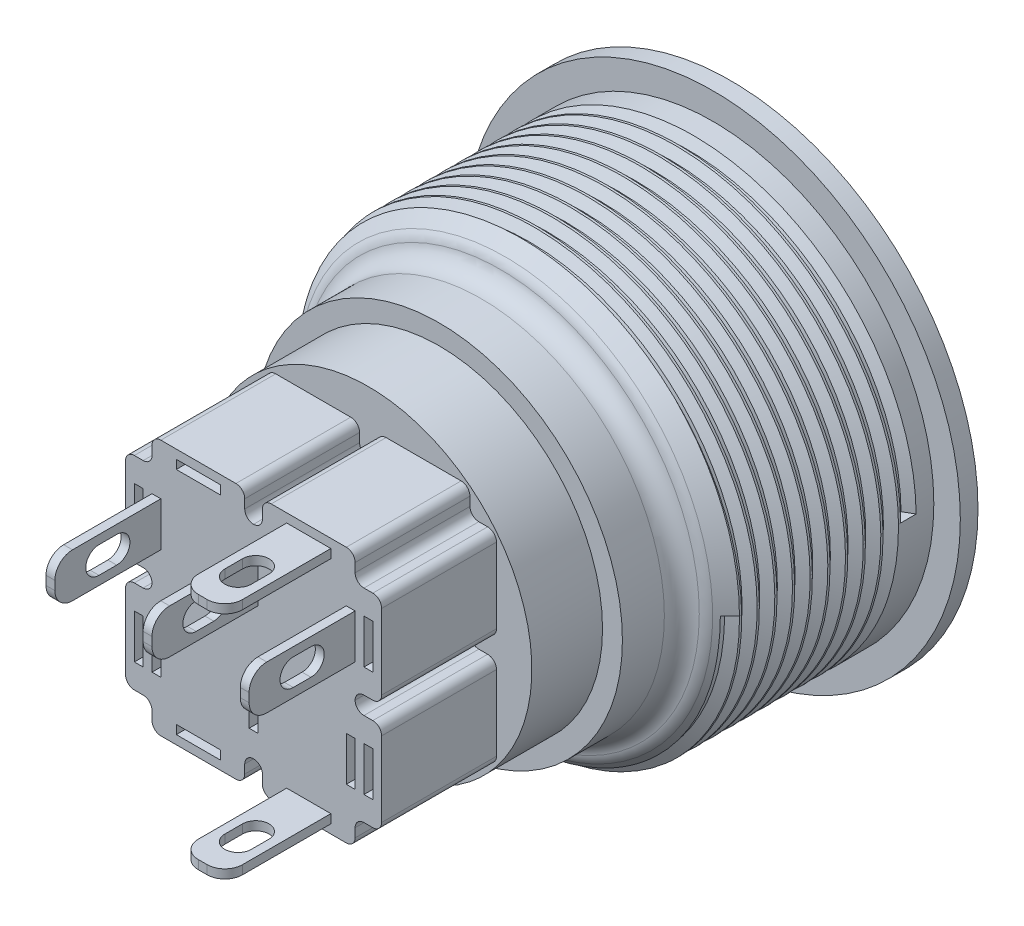
SolidWorks part; units mm, degrees
material "6061-O (SS)"
ref_plane "Ön Düzlem" through (0, 0, 0) normal (0, 0, 1) x (1, 0, 0)
ref_plane "Üst Düzlem" through (0, 0, 0) normal (0, 1, 0) x (1, 0, 0)
ref_plane "Sağ Düzlem" through (0, 0, 0) normal (1, 0, 0) x (0, 0, -1)
sketch "Çizim3" plane through (0, 0, 0) normal (0, 1, 0) x (1, 0, 0)
  line L0 (0, 0) -> (-14, 0) construction
  line L1 (-14, 0) -> (-14, 1) construction
  line L2 (-14, 1) -> (-12, 2) construction
  line L3 (-12, 2) -> (0, 2) construction
  line L4 (0, 2) -> (0, 0) construction
  line L5 (-11, 2) -> (-11, 0)
  line L6 (-11, 0) -> (-14, 0)
  line L7 (-14, 0) -> (-14, 1)
  line L8 (-14, 1) -> (-12, 2)
  line L9 (-12, 2) -> (-11, 2)
  dimension "D1" = 1
  dimension "D2" = 2
  dimension "D3" = 14
  dimension "D4" = 11
  dimension "D5" = 1
revolve "Döndür1" add sketch "Çizim3" angle 360 about L4
sketch "Çizim5" plane through (0, 0, 0) normal (0, 0, 1) x (1, 0, 0)
  circle A0 centre (0, 0) radius 11 construction
  circle A1 centre (0, 0) radius 11
extrude "Yükseklik-Ekstrüzyon2" add sketch "Çizim5" against normal blind 1.9
sketch "Çizim6" plane through (0, 0, -1.9) normal (0, 0, -1) x (-1, 0, 0)
  line L0 (0, 0) -> (-3.8891, 3.8891) construction
  line L1 (0, 0) -> (0, 5.5) construction
  line L2 (0, 0) -> (3.8891, 3.8891) construction
  line L3 (-3.5178, 3.5178) -> (-3.1623, 3.1623)
  line L4 (3.5178, 3.5178) -> (3.1623, 3.1623)
  line L5 (0, 6) -> (0, 1) construction
  line L6 (-0.75, 5.1059) -> (-0.75, 1.1059)
  line L7 (0.75, 5.1059) -> (0.75, 1.1059)
  line L8 (-0.25, 0.6059) -> (0.25, 0.6059)
  line L9 (-0.25, 5.6059) -> (0.25, 5.6059)
  line L10 (-0.75, 6) -> (-0.75, 1) construction
  line L11 (0.75, 6) -> (0.75, 1) construction
  arc A0 (-3.1252, 2.4966) -> (3.1252, 2.4966) centre (0, 0) ccw
  arc A1 (-4.2585, 3.4807) -> (4.2585, 3.4807) centre (0, 0) ccw
  circle A2 centre (0, 0) radius 5.5 construction
  circle A3 centre (0, 0) radius 4 construction
  arc A4 (3.5178, 3.5178) -> (4.2585, 3.4807) centre (3.8714, 3.1643) cw
  arc A5 (3.1623, 3.1623) -> (3.1252, 2.4966) centre (3.5158, 2.8087) ccw
  arc A6 (-3.1623, 3.1623) -> (-3.1252, 2.4966) centre (-3.5158, 2.8087) cw
  arc A7 (-3.5178, 3.5178) -> (-4.2585, 3.4807) centre (-3.8714, 3.1643) ccw
  arc A8 (-0.25, 0.6059) -> (-0.75, 1.1059) centre (-0.25, 1.1059) cw
  arc A9 (0.25, 0.6059) -> (0.75, 1.1059) centre (0.25, 1.1059) ccw
  arc A10 (0.75, 5.1059) -> (0.25, 5.6059) centre (0.25, 5.1059) ccw
  arc A11 (-0.25, 5.6059) -> (-0.75, 5.1059) centre (-0.25, 5.1059) ccw
  point P15 (2.8284, 2.8284)
  point P18 (-2.8284, 2.8284)
  point P22 (0, 3.5)
  point P26 (0, 3.5)
  dimension "D2" = 8
  dimension "D5" = 0.5
  dimension "D10" = 0.5
  dimension "D3" = 90
  dimension "D4" = 45
  dimension "D6" = 3.5
  dimension "D7" = 5
  dimension "D1" = 1.5
  dimension "D8" = 0.75
  dimension "D9" = 0.75
extrude "Kes-Ekstrüzyon1" cut sketch "Çizim6" against normal blind 0.01
sketch "Çizim8" plane through (0, 0, 0) normal (0, 0, 1) x (1, 0, 0)
  circle A0 centre (0, 0) radius 12.5
  dimension "D1" = 25
extrude "Yükseklik-Ekstrüzyon3" add sketch "Çizim8" along normal blind 12
chamfer "Pah1" distance 1 angle 45 1 edges at (12.5, 0, 12)
sketch "Çizim7" plane through (0, 0, -1.9) normal (0, 0, -1) x (-1, 0, 0)
  circle A0 centre (0, 0) radius 11 construction
  circle A1 centre (0, 0) radius 11
  circle A2 centre (0, 0) radius 9
  dimension "D1" = 2
extrude "Kes-Ekstrüzyon2" cut sketch "Çizim7" against normal blind 0.01
sketch "Çizim9" plane through (0, 0, 12) normal (0, 0, 1) x (1, 0, 0)
  circle A0 centre (0, 0) radius 10.375
  dimension "D1" = 20.75
extrude "Yükseklik-Ekstrüzyon4" add sketch "Çizim9" along normal blind 3.5
fillet "Radyus1" radius 1.125 1 edges at (10.375, 0, 12)
fillet "Radyus2" radius 1 1 edges at (11.5, 0, 12)
thread "Diş1" pitch 1 method cut profile "Diş Profili1" start angle 0, offset 1, length 10, pitch 1, diameter 25
ref_plane "Düzlem1" through (12.5, 0, 1) normal (0, -1, 0) x (1, 0, 0)
sketch "Diş Profili1" plane through (12.5, 0, 1) normal (0, -1, 0) x (1, 0, 0)
  line L0 (0, 0) -> (0, 1) construction
  line L11 (0, 0) -> (0, 0.875)
  line L12 (0, 0.875) -> (-0.5413, 0.5625)
  line L13 (-0.5413, 0.5625) -> (-0.5413, 0.3125)
  line L15 (-0.5413, 0.3125) -> (0, 0)
  line L17 (-0.5413, 0.4375) -> (0, 0.4375) construction
  point P2 (0, 0)
  dimension "Pitch" = 1
  dimension "Profile_Angle" = 60
  dimension "Profile_Land" = 0.25
  dimension "Profile_Height" = 0.5413
sketch "Çizim16" plane through (0, 0, 15.5) normal (0, 0, 1) x (1, 0, 0)
  circle A0 centre (0, 0) radius 9.25
  dimension "D1" = 18.5
extrude "Yükseklik-Ekstrüzyon5" add sketch "Çizim16" along normal blind 4
sketch "Çizim17" plane through (0, 0, 19.5) normal (0, 0, 1) x (1, 0, 0)
  line L0 (-7.2476, 5.7476) -> (-5.7476, 5.7476)
  line L1 (-5.7476, -7.2476) -> (-0.5, -7.2476)
  line L2 (-7.2476, -5.7476) -> (-7.2476, -0.5)
  line L3 (-5.7476, 7.2476) -> (-0.5, 7.2476)
  line L4 (7.2476, -5.7476) -> (7.2476, -0.5)
  line L5 (-5.7476, -5.7476) -> (5.7476, 5.7476) construction
  line L6 (-5.7476, 5.7476) -> (5.7476, -5.7476) construction
  line L7 (-5.7476, 5.7476) -> (-5.7476, 7.2476)
  line L8 (5.7476, 7.2476) -> (5.7476, 5.7476)
  line L9 (5.7476, 5.7476) -> (7.2476, 5.7476)
  line L10 (-7.2476, -5.7476) -> (-5.7476, -5.7476)
  line L11 (-5.7476, -5.7476) -> (-5.7476, -7.2476)
  line L12 (5.7476, -7.2476) -> (5.7476, -5.7476)
  line L13 (5.7476, -5.7476) -> (7.2476, -5.7476)
  line L14 (-7.2476, 0.5) -> (-5.7476, 0.5)
  line L15 (0.5, -7.2476) -> (0.5, -5.7476)
  line L16 (-0.5, -7.2476) -> (-0.5, -5.7476)
  line L17 (-0.5, -5.7476) -> (0.5, -5.7476)
  line L18 (0.5, -7.2476) -> (5.7476, -7.2476)
  line L19 (-5.7476, 0.5) -> (-5.7476, -0.5)
  line L20 (-7.2476, -0.5) -> (-5.7476, -0.5)
  line L21 (0.5, 7.2476) -> (0.5, 5.7476)
  line L22 (0.5, 5.7476) -> (-0.5, 5.7476)
  line L23 (-0.5, 7.2476) -> (-0.5, 5.7476)
  line L24 (7.2476, -0.5) -> (5.7476, -0.5)
  line L25 (5.7476, -0.5) -> (5.7476, 0.5)
  line L26 (7.2476, 0.5) -> (5.7476, 0.5)
  line L27 (-7.2476, 0.5) -> (-7.2476, 5.7476)
  line L28 (0.5, 7.2476) -> (5.7476, 7.2476)
  line L29 (7.2476, 0.5) -> (7.2476, 5.7476)
  circle A1 centre (0, 0) radius 9.25 construction
  circle A2 centre (0, 0) radius 1.3906 construction
  point P0 (0, 0)
  dimension "D2" = 1.5
  dimension "D3" = 1.5
  dimension "D4" = 4
  dimension "D5" = 1.5
  dimension "D6" = 1.5
  dimension "D7" = 1.5
  dimension "D8" = 1.5
extrude "Yükseklik-Ekstrüzyon6" add sketch "Çizim17" along normal blind 6.5
fillet "Radyus3" radius 0.5 28 edges at (7.2476, 0.5, 22.75) (5.7476, 0.5, 22.75) (5.7476, -0.5, 22.75) (7.2476, -0.5, 22.75) (7.2476, -5.7476, 22.75) (5.7476, -5.7476, 22.75) (5.7476, -7.2476, 22.75) (0.5, -7.2476, 22.75) (0.5, -5.7476, 22.75) (-0.5, -5.7476, 22.75) (-0.5, -7.2476, 22.75) (-5.7476, -7.2476, 22.75) (-5.7476, -5.7476, 22.75) (-7.2476, -5.7476, 22.75) (-7.2476, -0.5, 22.75) (-5.7476, -0.5, 22.75) (-5.7476, 0.5, 22.75) (-7.2476, 0.5, 22.75) (7.2476, 5.7476, 22.75) (5.7476, 5.7476, 22.75) (5.7476, 7.2476, 22.75) (0.5, 7.2476, 22.75) (-0.5, 7.2476, 22.75) (-0.5, 5.7476, 22.75) (0.5, 5.7476, 22.75) (-5.7476, 5.7476, 22.75) (-7.2476, 5.7476, 22.75) (-5.7476, 7.2476, 22.75)
sketch "Çizim18" plane through (0, 0, 26) normal (0, 0, 1) x (1, 0, 0)
  line L0 (-0.5, 6.4976) -> (-5.7476, 6.4976) construction
  line L1 (-0.5, 6.2476) -> (-0.5, 6.7476) construction
  line L2 (-5.7476, 6.7476) -> (-5.7476, 6.2476) construction
  line L3 (-1.8738, 6.4976) -> (-4.3738, 6.4976) construction
  line L4 (-1.8738, 6.7476) -> (-4.3738, 6.7476)
  line L5 (-1.8738, 6.2476) -> (-4.3738, 6.2476)
  line L6 (-1.8738, 6.7476) -> (-1.8738, 6.2476)
  line L7 (-4.3738, 6.7476) -> (-4.3738, 6.2476)
  line L8 (0.5, 6.4976) -> (5.7476, 6.4976) construction
  line L9 (0.5, 6.7476) -> (0.5, 6.2476) construction
  line L10 (5.7476, 6.2476) -> (5.7476, 6.7476) construction
  line L11 (4.3738, 6.4976) -> (1.8738, 6.4976) construction
  line L12 (4.3738, 6.7476) -> (1.8738, 6.7476)
  line L13 (4.3738, 6.2476) -> (1.8738, 6.2476)
  line L14 (1.8738, 6.7476) -> (1.8738, 6.2476)
  line L15 (4.3738, 6.7476) -> (4.3738, 6.2476)
  line L16 (6.7476, 4.3738) -> (6.2476, 4.3738)
  line L17 (6.2476, 1.8738) -> (6.2476, 4.3738)
  line L18 (6.7476, 1.8738) -> (6.2476, 1.8738)
  line L19 (6.7476, 1.8738) -> (6.7476, 4.3738)
  line L20 (6.7476, -1.8738) -> (6.2476, -1.8738)
  line L21 (6.2476, -4.3738) -> (6.2476, -1.8738)
  line L22 (6.7476, -4.3738) -> (6.2476, -4.3738)
  line L23 (6.7476, -4.3738) -> (6.7476, -1.8738)
  line L24 (4.3738, -6.7476) -> (4.3738, -6.2476)
  line L25 (1.8738, -6.2476) -> (4.3738, -6.2476)
  line L26 (1.8738, -6.7476) -> (1.8738, -6.2476)
  line L27 (1.8738, -6.7476) -> (4.3738, -6.7476)
  line L28 (-1.8738, -6.7476) -> (-1.8738, -6.2476)
  line L29 (-4.3738, -6.2476) -> (-1.8738, -6.2476)
  line L30 (-4.3738, -6.7476) -> (-4.3738, -6.2476)
  line L31 (-4.3738, -6.7476) -> (-1.8738, -6.7476)
  line L32 (-6.7476, -4.3738) -> (-6.2476, -4.3738)
  line L33 (-6.2476, -1.8738) -> (-6.2476, -4.3738)
  line L34 (-6.7476, -1.8738) -> (-6.2476, -1.8738)
  line L35 (-6.7476, -1.8738) -> (-6.7476, -4.3738)
  line L36 (-6.7476, 1.8738) -> (-6.2476, 1.8738)
  line L37 (-6.2476, 4.3738) -> (-6.2476, 1.8738)
  line L38 (-6.7476, 4.3738) -> (-6.2476, 4.3738)
  line L39 (-6.7476, 4.3738) -> (-6.7476, 1.8738)
  line L40 (-7.2476, 5.2476) -> (-7.2476, 1) construction
  line L41 (-5.7476, 1.8738) -> (-5.2476, 1.8738)
  line L42 (-5.2476, 4.3738) -> (-5.2476, 1.8738)
  line L43 (-5.7476, 4.3738) -> (-5.2476, 4.3738)
  line L44 (-5.7476, 4.3738) -> (-5.7476, 1.8738)
  line L45 (-5.7476, -4.3738) -> (-5.2476, -4.3738)
  line L46 (-5.2476, -1.8738) -> (-5.2476, -4.3738)
  line L47 (-5.7476, -1.8738) -> (-5.2476, -1.8738)
  line L48 (-5.7476, -1.8738) -> (-5.7476, -4.3738)
  line L49 (5.7476, 4.3738) -> (5.2476, 4.3738)
  line L50 (5.2476, 1.8738) -> (5.2476, 4.3738)
  line L51 (5.7476, 1.8738) -> (5.2476, 1.8738)
  line L52 (5.7476, 1.8738) -> (5.7476, 4.3738)
  line L53 (5.7476, -1.8738) -> (5.2476, -1.8738)
  line L54 (5.2476, -4.3738) -> (5.2476, -1.8738)
  line L55 (5.7476, -4.3738) -> (5.2476, -4.3738)
  line L56 (5.7476, -4.3738) -> (5.7476, -1.8738)
  line L57 (3.1238, -6.2476) -> (3.1238, -6.7476) construction
  line L58 (3.1238, 6.7476) -> (3.1238, 6.2476) construction
  line L59 (5.2476, 3.1238) -> (-5.2476, 3.1238) construction
  line L60 (-0.25, 3.1238) -> (0.25, 3.1238) construction
  line L61 (-0.25, 4.3738) -> (-0.25, 1.8738)
  line L62 (0.25, 4.3738) -> (0.25, 1.8738)
  line L63 (-0.25, 1.8738) -> (0.25, 1.8738)
  line L64 (-0.25, 4.3738) -> (0.25, 4.3738)
  line L65 (0, 0) -> (5.7476, 0) construction
  line L66 (-0.25, -4.3738) -> (-0.25, -1.8738)
  line L67 (-0.25, -1.8738) -> (0.25, -1.8738)
  line L68 (0.25, -4.3738) -> (0.25, -1.8738)
  line L69 (-0.25, -4.3738) -> (0.25, -4.3738)
  point P9 (-3.1238, 6.4976)
  point P22 (3.1238, 6.4976)
  point P78 (3.1238, 0)
  point P79 (0.9405, 2.8845)
  dimension "D1" = 2.5
  dimension "D7" = 0.5
  dimension "D10" = 2.5
  dimension "D11" = 0.5
  dimension "D12" = 2.5
  dimension "D2" = 0.25
  dimension "D3" = 0.25
  dimension "D4" = 0.25
  dimension "D5" = 0.25
  dimension "D8" = 2
  dimension "D9" = 2
  dimension "D6" = 4
extrude "Kes-Ekstrüzyon3" cut sketch "Çizim18" against normal blind 1
sketch "Çizim21" plane through (0, 0, 25) normal (0, 0, 1) x (1, 0, 0)
  line L4 (-5.7476, 4.3738) -> (-5.7476, 1.8738)
  line L5 (-5.7476, 1.8738) -> (-5.2476, 1.8738)
  line L6 (-5.2476, 1.8738) -> (-5.2476, 4.3738)
  line L7 (-5.2476, 4.3738) -> (-5.7476, 4.3738)
  line L8 (-5.7476, 4.3738) -> (-5.7476, 1.8738)
  line L9 (-5.7476, 1.8738) -> (-5.2476, 1.8738)
  line L10 (-5.2476, 1.8738) -> (-5.2476, 4.3738)
  line L11 (-5.2476, 4.3738) -> (-5.7476, 4.3738)
  line L12 (0.25, 4.3738) -> (-0.25, 4.3738)
  line L13 (-0.25, 4.3738) -> (-0.25, 1.8738)
  line L14 (-0.25, 1.8738) -> (0.25, 1.8738)
  line L15 (0.25, 1.8738) -> (0.25, 4.3738)
  line L16 (0.25, 4.3738) -> (-0.25, 4.3738)
  line L17 (-0.25, 4.3738) -> (-0.25, 1.8738)
  line L18 (-0.25, 1.8738) -> (0.25, 1.8738)
  line L19 (0.25, 1.8738) -> (0.25, 4.3738)
  line L20 (5.7476, 1.8738) -> (5.7476, 4.3738)
  line L21 (5.7476, 4.3738) -> (5.2476, 4.3738)
  line L22 (5.2476, 4.3738) -> (5.2476, 1.8738)
  line L23 (5.2476, 1.8738) -> (5.7476, 1.8738)
  line L24 (5.7476, 1.8738) -> (5.7476, 4.3738)
  line L25 (5.7476, 4.3738) -> (5.2476, 4.3738)
  line L26 (5.2476, 4.3738) -> (5.2476, 1.8738)
  line L27 (5.2476, 1.8738) -> (5.7476, 1.8738)
  line L28 (4.3738, 6.2476) -> (4.3738, 6.7476)
  line L29 (4.3738, 6.7476) -> (1.8738, 6.7476)
  line L30 (1.8738, 6.7476) -> (1.8738, 6.2476)
  line L31 (1.8738, 6.2476) -> (4.3738, 6.2476)
  line L32 (4.3738, 6.2476) -> (4.3738, 6.7476)
  line L33 (4.3738, 6.7476) -> (1.8738, 6.7476)
  line L34 (1.8738, 6.7476) -> (1.8738, 6.2476)
  line L35 (1.8738, 6.2476) -> (4.3738, 6.2476)
  line L36 (1.8738, -6.7476) -> (4.3738, -6.7476)
  line L37 (4.3738, -6.7476) -> (4.3738, -6.2476)
  line L38 (4.3738, -6.2476) -> (1.8738, -6.2476)
  line L39 (1.8738, -6.2476) -> (1.8738, -6.7476)
  line L40 (1.8738, -6.7476) -> (4.3738, -6.7476)
  line L41 (4.3738, -6.7476) -> (4.3738, -6.2476)
  line L42 (4.3738, -6.2476) -> (1.8738, -6.2476)
  line L43 (1.8738, -6.2476) -> (1.8738, -6.7476)
  dimension "D1" = 0
  dimension "D2" = 0
  dimension "D3" = 0
  dimension "D4" = 0
  dimension "D5" = 0
extrude "Yükseklik-Ekstrüzyon7" add sketch "Çizim21" along normal blind 7
sketch "Çizim22" plane through (0, -6.7476, 0) normal (0, -1, 0) x (1, 0, 0)
  line L0 (1.8738, 29.5) -> (4.3738, 29.5) construction
  line L1 (1.8738, 32) -> (1.8738, 26) construction
  line L2 (4.3738, 32) -> (4.3738, 26) construction
  line L3 (3.8738, 29.5) -> (2.3738, 29.5) construction
  line L4 (3.1238, 30) -> (3.1238, 29) construction
  line L5 (3.8738, 30) -> (3.8738, 29)
  line L6 (2.3738, 30) -> (2.3738, 29)
  line L7 (3.1238, 32) -> (3.1238, 29.5) construction
  line L8 (1.8738, 32) -> (4.3738, 32) construction
  arc A0 (3.8738, 30) -> (2.3738, 30) centre (3.1238, 30) ccw
  arc A1 (2.3738, 29) -> (3.8738, 29) centre (3.1238, 29) ccw
  point P9 (3.1238, 29.5)
  point P11 (3.1238, 29.5)
  dimension "D2" = 1
  dimension "D3" = 2.5
  dimension "D1" = 1.5
extrude "Kes-Ekstrüzyon4" cut sketch "Çizim22" against normal blind 16 contours L5 A0 L6 L3 | L6 A1 L5 L3 region at (3.1238, -6.7476, 29.5)
sketch "Çizim23" plane through (-5.7476, 0, 0) normal (-1, 0, 0) x (0, 0, 1)
  line L0 (29, 4.3738) -> (29, 1.8738) construction
  line L1 (29, 2.3738) -> (29, 3.8738) construction
  line L2 (29.5, 3.1238) -> (28.5, 3.1238) construction
  line L3 (29.5, 2.3738) -> (28.5, 2.3738)
  line L4 (29.5, 3.8738) -> (28.5, 3.8738)
  line L5 (31.5, 3.1238) -> (29, 3.1238) construction
  arc A0 (29.5, 2.3738) -> (29.5, 3.8738) centre (29.5, 3.1238) ccw
  arc A1 (28.5, 3.8738) -> (28.5, 2.3738) centre (28.5, 3.1238) ccw
  point P5 (29, 3.1238)
  point P7 (29, 3.1238)
extrude "Kes-Ekstrüzyon5" cut sketch "Çizim23" against normal blind 16
fillet "Radyus4" radius 1 10 edges at (1.8738, -6.4976, 32) (4.3738, -6.4976, 32) (-5.4976, 4.3738, 32) (-5.4976, 1.8738, 32) (5.4976, 1.8738, 32) (5.4976, 4.3738, 32) (0, 1.8738, 32) (0, 4.3738, 32) (1.8738, 6.4976, 32) (4.3738, 6.4976, 32)
